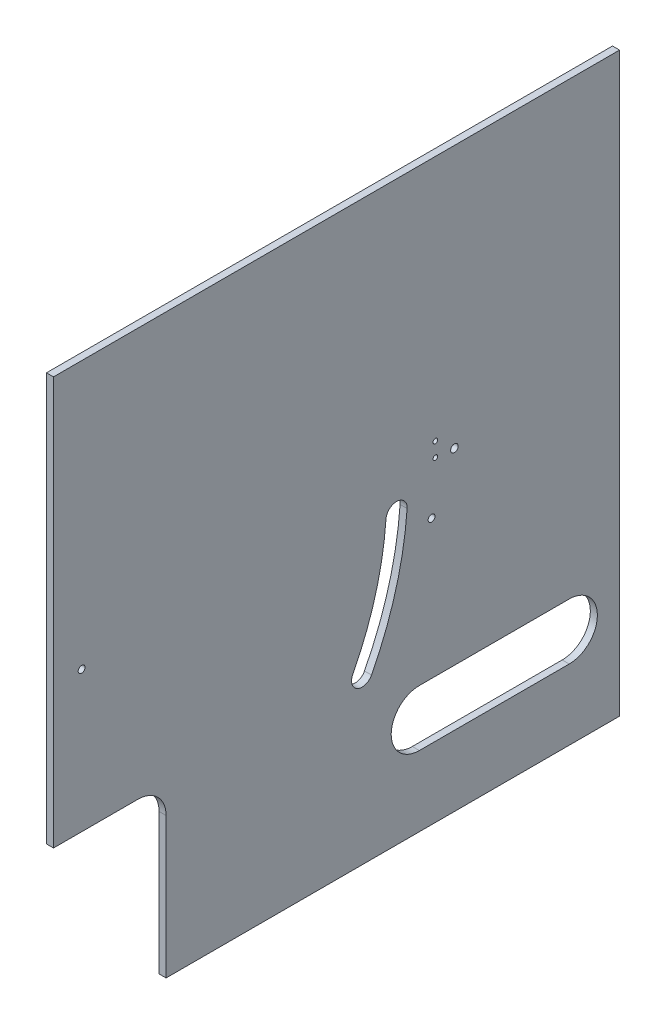
SolidWorks part; units mm, degrees
material "Acrylic (Medium-high impact)"
ref_plane "Front" through (0, 0, 0) normal (0, 0, 1) x (1, 0, 0)
ref_plane "Top" through (0, 0, 0) normal (0, 1, 0) x (1, 0, 0)
ref_plane "Right" through (0, 0, 0) normal (1, 0, 0) x (0, 0, -1)
sketch "Sketch1" plane through (0, 0, 0) normal (1, 0, 0) x (0, 0, -1)
  line L1 (-127.725, 130.175) -> (127.725, 130.175)
  line L2 (-127.725, 130.175) -> (-127.725, -130.175)
  line L3 (-127.725, -130.175) -> (127.725, -130.175)
  line L4 (127.725, 130.175) -> (127.725, -130.175)
  point P4 (-127.725, 0)
  point P6 (0, 130.175)
  dimension "D1" = 260.35
  dimension "D2" = 255.45
extrude "Boss-Extrude1" add sketch "Sketch1" along normal blind 3.175
sketch "Sketch2" plane through (3.175, 0, 0) normal (1, 0, 0) x (0, 0, -1)
  line L0 (127.725, -130.175) -> (127.725, 130.175) construction
  line L1 (-127.725, 130.175) -> (127.725, 130.175)
  line L2 (-127.725, 130.175) -> (-127.725, 123.825)
  line L3 (-127.725, 123.825) -> (127.725, 123.825)
  line L4 (127.725, 130.175) -> (127.725, 123.825)
  dimension "D1" = 6.35
extrude "Boss-Extrude2" add sketch "Sketch2" along normal blind 12.7
sketch "Sketch3" plane through (0, 0, 0) normal (-1, 0, 0) x (0, 0, 1)
  line L0 (-105.025, -73.025) -> (-37.375, -73.025)
  line L1 (-37.375, -98.425) -> (-105.025, -98.425)
  line L2 (0.725, 130.175) -> (0.725, -130.175) construction
  line L3 (-127.725, 130.175) -> (127.725, 130.175) construction
  line L4 (127.725, -130.175) -> (-127.725, -130.175) construction
  line L5 (127.725, 130.175) -> (127.725, -130.175) construction
  arc A0 (-37.375, -73.025) -> (-37.375, -98.425) centre (-37.375, -85.725) cw
  arc A1 (-105.025, -98.425) -> (-105.025, -73.025) centre (-105.025, -85.725) cw
  dimension "D1" = 25.4
  dimension "D3" = 232.75
  dimension "D2" = 38.1
  dimension "D4" = 127
  dimension "D5" = 44.45
extrude "Cut-Extrude1" cut sketch "Sketch3" against normal through all
sketch "Sketch5" plane through (0, 0, -127.725) normal (0, 0, -1) x (-1, 0, 0)
  line L1 (-3.175, 123.825) -> (-57.7651, 123.825)
  line L2 (-3.175, 123.825) -> (-3.175, 157.6842)
  line L3 (-3.175, 157.6842) -> (-57.7651, 157.6842)
  line L4 (-57.7651, 123.825) -> (-57.7651, 157.6842)
extrude "Cut-Extrude2" cut sketch "Sketch5" against normal through all
sketch "Sketch6" plane through (3.175, 0, 0) normal (1, 0, 0) x (0, 0, -1)
  line L0 (89.875, -88.265) -> (89.875, -83.185)
  line L1 (111.875, -83.185) -> (111.875, -88.265)
  line L2 (83.875, -103.765) -> (83.875, -98.685)
  line L3 (86.875, -103.765) -> (86.875, -98.685)
  line L4 (83.875, -72.765) -> (83.875, -67.685)
  line L5 (86.875, -72.765) -> (86.875, -67.685)
  line L6 (100.875, -83.185) -> (100.875, -88.265) construction
  line L7 (117.875, -103.765) -> (117.875, -98.685)
  line L8 (114.875, -103.765) -> (114.875, -98.685)
  line L9 (114.875, -72.765) -> (114.875, -67.685)
  line L10 (117.875, -72.765) -> (117.875, -67.685)
  line L11 (-127.725, 130.175) -> (-127.725, -130.175) construction
  line L12 (-127.725, -130.175) -> (127.725, -130.175) construction
  arc A0 (89.875, -88.265) -> (111.875, -88.265) centre (100.875, -88.265) ccw
  arc A1 (111.875, -83.185) -> (89.875, -83.185) centre (100.875, -83.185) ccw
  arc A2 (83.875, -103.765) -> (86.875, -103.765) centre (85.375, -103.765) ccw
  arc A3 (86.875, -98.685) -> (83.875, -98.685) centre (85.375, -98.685) ccw
  arc A4 (83.875, -72.765) -> (86.875, -72.765) centre (85.375, -72.765) ccw
  arc A5 (86.875, -67.685) -> (83.875, -67.685) centre (85.375, -67.685) ccw
  arc A6 (117.875, -103.765) -> (114.875, -103.765) centre (116.375, -103.765) cw
  arc A7 (114.875, -98.685) -> (117.875, -98.685) centre (116.375, -98.685) cw
  arc A8 (117.875, -72.765) -> (114.875, -72.765) centre (116.375, -72.765) cw
  arc A9 (114.875, -67.685) -> (117.875, -67.685) centre (116.375, -67.685) cw
  circle A10 centre (85.375, -69.36) radius 3.175
  circle A11 centre (116.375, -69.36) radius 3.175
  circle A12 centre (85.375, -102.09) radius 3.175
  circle A13 centre (116.375, -102.09) radius 3.175
  point P37 (100.875, -85.725)
  point P38 (111.875, -85.725)
  dimension "D5" = 1.5
  dimension "D9" = 1.5
  dimension "D12" = 6.35
  dimension "D1" = 5.08
  dimension "D2" = 5.08
  dimension "D3" = 15.5
  dimension "D4" = 15.5
  dimension "D6" = 15.5
  dimension "D7" = 15.5
  dimension "D8" = 5.08
  dimension "D10" = 228.6
  dimension "D11" = 44.45
extrude "Cut-Extrude5" [suppressed] cut sketch "Sketch6" against normal through all contours L5 A10 A5 | L4 A10 L5 A5 | A5 A10 L4 | L9 A11 L10 A9 | A9 A11 L9 | L10 A11 A9 | A2 A12 L3 | L3 A12 L2 A2 | L2 A12 A2 | L7 A13 L8 A6 | A6 A13 L7 | L8 A13 A6
sketch "Sketch7" plane through (3.175, 0, 0) normal (1, 0, 0) x (0, 0, -1)
  line L0 (-127.725, 130.175) -> (-127.725, -130.175) construction
  line L1 (-127.725, -123.825) -> (127.725, -123.825)
  line L2 (-127.725, -123.825) -> (-127.725, -130.175)
  line L3 (-127.725, -130.175) -> (127.725, -130.175)
  line L4 (127.725, -123.825) -> (127.725, -130.175)
  line L5 (-127.725, -130.175) -> (127.725, -130.175) construction
  line L6 (127.725, -130.175) -> (127.725, 130.175) construction
  dimension "D1" = 6.35
extrude "Cut-Extrude6" [suppressed] cut sketch "Sketch7" against normal through all
sketch "Sketch8" plane through (0, 0, 0) normal (-1, 0, 0) x (0, 0, 1)
  line L0 (127.725, 130.175) -> (127.725, -130.175) construction
  line L1 (127.725, -130.175) -> (-127.725, -130.175) construction
  line L3 (127.725, -130.175) -> (-127.725, -130.175) construction
  circle A0 centre (115.025, 9.525) radius 1.55
  circle A3 centre (-53.205, 11.825) radius 1.7
  circle A4 centre (-42.905, -10.375) radius 1.55
  circle A5 centre (-44.605, 18.925) radius 1.05
  circle A6 centre (-44.605, 12.425) radius 1.05
  point P11 (-36.105, 22.225)
  dimension "D1" = 3.1
  dimension "D4" = 10.3
  dimension "D5" = 17.1
  dimension "D10" = 3.1
  dimension "D11" = 3.4
  dimension "D14" = 22.2
  dimension "D15" = 3.3
  dimension "D8" = 2.1
  dimension "D2" = 12.7
  dimension "D3" = 139.7
  dimension "D6" = 151.13
  dimension "D7" = 152.4
  dimension "D9" = 6.5
  dimension "D12" = 8.5
  dimension "D13" = 32.6
extrude "Cut-Extrude7" cut sketch "Sketch8" against normal through all
sketch "Sketch9" plane through (0, 0, 0) normal (-1, 0, 0) x (0, 0, 1)
  line L0 (127.725, 130.175) -> (127.725, -130.175) construction
  line L1 (127.725, -53.975) -> (76.925, -53.975)
  line L2 (127.725, -53.975) -> (127.725, -130.175)
  line L3 (127.725, -130.175) -> (76.925, -130.175)
  line L4 (76.925, -53.975) -> (76.925, -130.175)
  line L5 (127.725, -130.175) -> (-127.725, -130.175) construction
  dimension "D1" = 50.8
  dimension "D2" = 76.2
extrude "Cut-Extrude8" cut sketch "Sketch9" against normal through all
fillet "Fillet1" radius 12.7 1 edges at (1.5875, -53.975, 76.925)
sketch "Sketch10" plane through (0, 0, 0) normal (-1, 0, 0) x (0, 0, 1)
  line L3 (-31.867, -1.0885) -> (-22.342, -0.4003) construction
  line L4 (-9.3573, -130.175) -> (-9.3573, -60.175) construction
  line L5 (76.925, -130.175) -> (-127.725, -130.175) construction
  line L6 (-15.792, -58.1271) -> (-7.3094, -53.7403) construction
  arc A2 (-15.792, -58.1271) -> (-7.3094, -53.7403) centre (-11.5507, -55.9337) ccw
  arc A4 (-31.867, -1.0885) -> (-15.792, -58.1271) centre (115.025, 9.525) ccw
  arc A5 (-22.342, -0.4003) -> (-7.3094, -53.7403) centre (115.025, 9.525) ccw
  arc A7 (-22.342, -0.4003) -> (-31.867, -1.0885) centre (-27.1045, -0.7444) ccw
  circle A8 centre (115.025, 9.525) radius 142.5 construction
  point P11 (0, 0)
  point P12 (109.6198, 8.3457)
  point P13 (109.6198, 8.3457)
  point P14 (-21.4997, 9.2684)
  point P17 (-8.3426, -46.7033)
  point P18 (0, 0)
  point P19 (0, -49.2638)
  point P20 (-10.4681, -46.6687)
  point P21 (-15.172, -5.8839)
  point P22 (-28.8036, 11.9508)
  point P23 (0, 0)
  point P24 (-9.3573, -60.175)
  dimension "D1" = 285
  dimension "D2" = 9.525
  dimension "D3" = 53.34
  dimension "D5" = 70
extrude "Cut-Extrude9" cut sketch "Sketch10" against normal through all
equation "\"bottomThickness\"= .25in"
equation "\"wallThickness\"= .125in"
equation "\"D1@Boss-Extrude1\"=\"wallThickness\""
